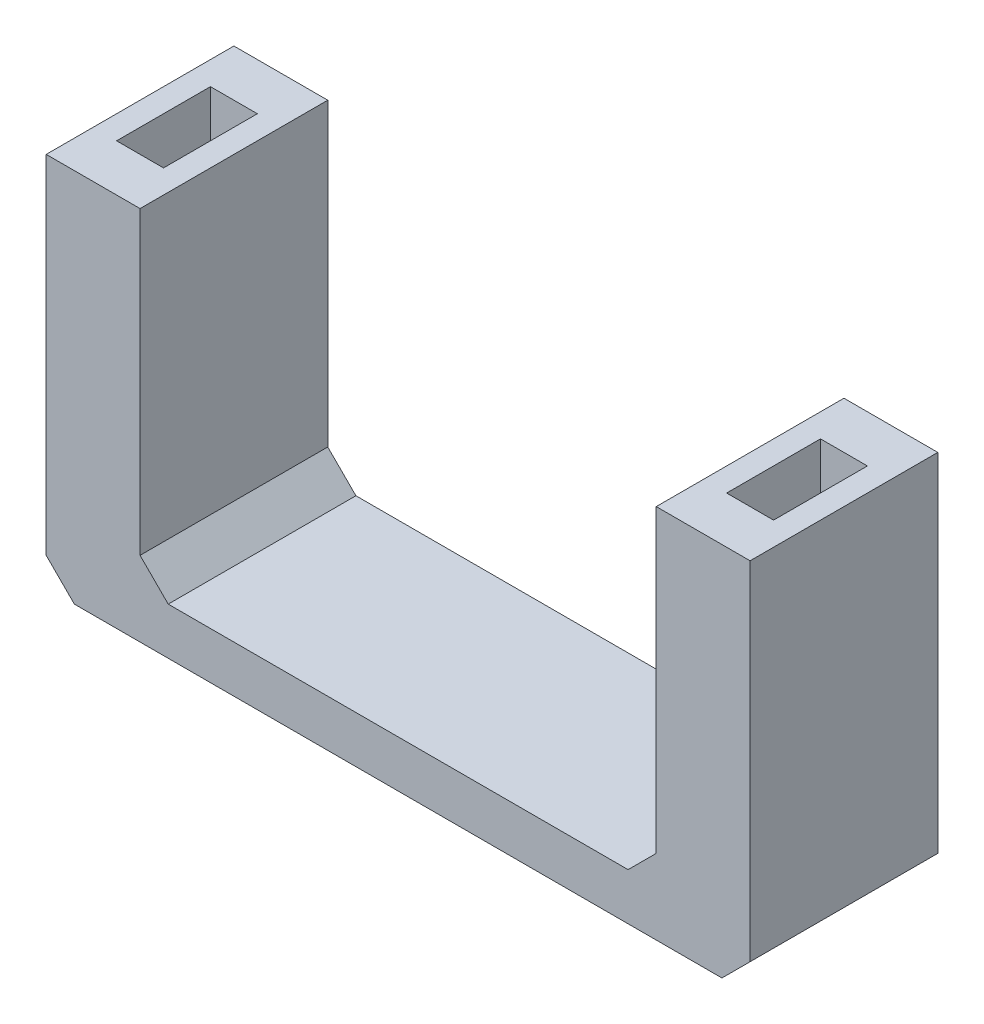
SolidWorks part; units mm, degrees
material "1060 Alloy"
ref_plane "Front" through (0, 0, 0) normal (0, 0, 1) x (1, 0, 0)
ref_plane "Top" through (0, 0, 0) normal (0, 1, 0) x (1, 0, 0)
ref_plane "Right" through (0, 0, 0) normal (1, 0, 0) x (0, 0, -1)
sketch "Sketch1" plane through (0, 0, 0) normal (0, 1, 0) x (1, 0, 0)
  circle A0 centre (0, 0) radius 250
  dimension "D1" = 500
extrude "Boss-Extrude1" add sketch "Sketch1" along normal blind 250
sketch "Sketch3" plane through (0, 250, 0) normal (0, 1, 0) x (1, 0, 0)
  line L1 (-1375, -500) -> (1375, -500)
  line L2 (-1375, -500) -> (-1375, 500)
  line L3 (-1375, 500) -> (1375, 500)
  line L4 (1375, -500) -> (1375, 500)
  line L5 (-1375, -500) -> (1375, 500) construction
  line L6 (-1375, 500) -> (1375, -500) construction
  point P0 (0, 0)
  dimension "D1" = 2750
  dimension "D2" = 1000
extrude "Boss-Extrude3" add sketch "Sketch3" along normal mid plane 250
sketch "Sketch4" plane through (1375, 0, 0) normal (1, 0, 0) x (0, 0, -1)
  line L0 (500, 375) -> (500, 125) construction
  line L1 (-500, 125) -> (500, 125)
  line L2 (-500, 125) -> (-500, 2125)
  line L3 (-500, 2125) -> (500, 2125)
  line L4 (500, 125) -> (500, 2125)
  dimension "D1" = 2000
extrude "Boss-Extrude4" add sketch "Sketch4" along normal blind 500
sketch "Sketch6" plane through (0, 125, 0) normal (0, -1, 0) x (1, 0, 0)
  line L0 (1375, 0) -> (1875, 0) construction
  line L1 (1500, -250) -> (1750, -250)
  line L2 (1500, -250) -> (1500, 250)
  line L3 (1500, 250) -> (1750, 250)
  line L4 (1375, 500) -> (1375, -500)
  line L5 (1875, 500) -> (1375, 500)
  line L6 (1875, -500) -> (1875, 500)
  line L7 (1375, -500) -> (1875, -500)
  line L8 (1375, 500) -> (1375, -500) construction
  line L9 (1875, 500) -> (1375, 500) construction
  line L10 (1875, -500) -> (1875, 500) construction
  line L11 (1375, -500) -> (1875, -500) construction
  line L12 (1750, -250) -> (1750, 250)
  line L13 (1500, -250) -> (1750, 250) construction
  line L14 (1500, 250) -> (1750, -250) construction
  line L15 (1625, 500) -> (1625, -500) construction
  point P2 (1625, 0)
  dimension "D2" = 500
  dimension "D3" = 250
  dimension "D1" = 0
extrude "Cut-Extrude1" cut sketch "Sketch6" against normal blind 2597
sketch "Sketch7" plane through (0, 125, 0) normal (0, -1, 0) x (1, 0, 0)
  line L1 (1500, -250) -> (1750, -250) construction
  line L3 (1750, 250) -> (1500, 250) construction
  line L4 (1625, 250) -> (1625, -250) construction
  line L5 (1750, 0) -> (1500, 0) construction
  line L6 (1750, -250) -> (1750, 250) construction
  line L7 (1500, 250) -> (1500, -250) construction
  line L9 (1500, -400) -> (1750, -400)
  line L10 (1500, -400) -> (1500, 400)
  line L11 (1500, 400) -> (1750, 400)
  line L12 (1750, -400) -> (1750, 400)
  line L13 (1500, -400) -> (1750, 400) construction
  line L14 (1500, 400) -> (1750, -400) construction
  point P12 (1625, 0)
  dimension "D1" = 250
  dimension "D2" = 800
extrude "Cut-Extrude2" cut sketch "Sketch7" against normal blind 1750
chamfer "Chamfer1" distance 150 angle 45 2 edges at (1875, 125, 0) (1375, 375, 0)
mirror "Mirror1" about plane through (0, 0, 0) normal (1, 0, 0) of "Cut-Extrude2", "Cut-Extrude1", "Boss-Extrude4", "Chamfer1"
equation "\"BaseDiameter\"= .5"
equation "\"D1@Sketch1\"=\"BaseDiameter\""
equation "\"BaseHeight\"=0.25"
equation "\"D1@Boss-Extrude1\"=\"BaseHeight\""
equation "\"topdiameter\"=1"
equation "\"topheight\"=0.25"
